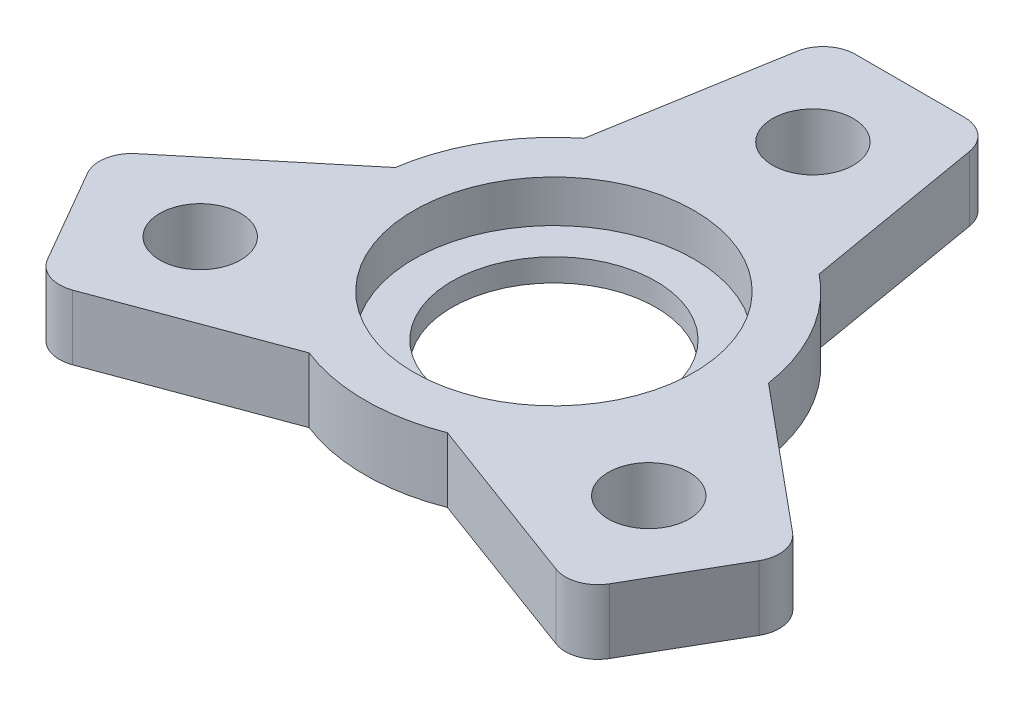
SolidWorks part; units mm, degrees
ref_plane "Front Plane" through (0, 0, 0) normal (0, 0, 1) x (1, 0, 0)
ref_plane "Top Plane" through (0, 0, 0) normal (0, 1, 0) x (1, 0, 0)
ref_plane "Right Plane" through (0, 0, 0) normal (1, 0, 0) x (0, 0, -1)
sketch "Sketch2" plane through (0, 0, 0) normal (0, 1, 0) x (1, 0, 0)
  line L0 (0, 0) -> (0, 20.32) construction
  line L1 (-9.2221, 11.5883) -> (-6.4286, 27.94)
  line L2 (-6.4286, 27.94) -> (6.4286, 27.94)
  line L4 (9.2221, 11.5883) -> (6.4286, 27.94)
  circle A0 centre (0, 20.32) radius 12.7 construction
  circle A1 centre (0, 20.32) radius 3.5179 construction
  circle A2 centre (0, 0) radius 11
  circle A3 centre (0, 0) radius 20.955 construction
  circle A6 centre (17.5976, -10.16) radius 12.7 construction
  circle A7 centre (0, 0) radius 8
  circle A8 centre (0, 0) radius 20.32 construction
  circle A9 centre (0, 0) radius 14.81
  circle A10 centre (-17.5976, -10.16) radius 12.7 construction
  circle A11 centre (0, 0) radius 4 construction
  point P15 (0, 0)
  point P16 (0, 20.32)
  point P20 (-9.0139, 10.1035)
  point P21 (0, 20.32)
  point P23 (0, 27.94)
  point P24 (-6.6551, 25.4)
  dimension "D3" = 25.4
  dimension "D2" = 7.0358
  dimension "D4" = 22
  dimension "D5" = 41.91
  dimension "D6" = 3
  dimension "D8" = 16
  dimension "D9" = 3.81
  dimension "D10" = 7.62
  dimension "D11" = 7.62
  dimension "D7" = 8
  dimension "D1" = 20.32
extrude "Boss-Extrude1" add sketch "Sketch2" along normal blind 5.08 contours A9 | A9 A2 region at (0, 0, -20.481) region at (0, 0, -14.3911)
extrude "Boss-Extrude2" add sketch "Sketch2<6>" along normal blind 1.778 contours A2 A7 region at (-10.6889, 0, 0)
sketch "Sketch2<6>" plane through (0, 0, 0) normal (0, 1, 0) x (1, 0, 0) same geometry as "Sketch2"
hole_wizard "1/4 (0.25) Diameter Hole3" positions "3DSketch3" profile "Sketch5" hole size "1/4" standard "ANSI Inch" end condition through all
sketch3d "3DSketch3"
  point P0 (0, 0, -20.32)
  point P4 (0, 0, -20.32)
  point P6 (0, 0, -20.32)
  point P9 (0, 0, -19.05)
sketch "Sketch5" plane through (0, 0, -20.32) normal (1, 0, 0) x (0, 0, -1)
  line L0 (0, 0) -> (0, 5.08)
  line L1 (0, 5.08) -> (3.175, 5.08)
  line L2 (3.175, 5.08) -> (3.175, 0)
  line L5 (3.175, 0) -> (0, 0)
  line L11 (0, -6.35) -> (0, 107.95) construction
  dimension "Thru Hole Dia." = 6.35
  dimension "Thru Hole Depth" = 5.08
fillet "Fillet3" radius 2.54 2 edges at (6.4286, 2.54, -27.94) (-6.4286, 2.54, -27.94)
pattern_circular "CirPattern2" count 3 over 360 about axis through (0, 1.778, 0) along (0, -1, 0) of "Boss-Extrude1", "1/4 (0.25) Diameter Hole3", "Fillet3" reverse direction yes
